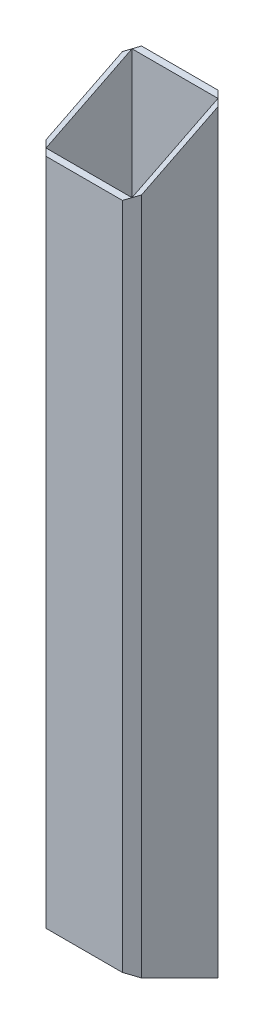
SolidWorks part; units mm, degrees
ref_plane "Front Plane" through (0, 0, 0) normal (0, 0, 1) x (1, 0, 0)
ref_plane "Top Plane" through (0, 0, 0) normal (0, 1, 0) x (1, 0, 0)
ref_plane "Right Plane" through (0, 0, 0) normal (1, 0, 0) x (0, 0, -1)
sketch "Sketch1" plane through (0, 0, 0) normal (0, 0, 1) x (1, 0, 0)
  line L1 (0, 0) -> (50, 0)
  line L2 (0, 0) -> (0, 400)
  line L3 (0, 400) -> (50, 400)
  line L4 (50, 0) -> (50, 400)
  dimension "D1" = 400
  dimension "D2" = 50
extrude "Boss-Extrude2" add sketch "Sketch1" along normal blind 50
sketch "Sketch2" plane through (0, 0, 0) normal (0, -1, 0) x (1, 0, 0)
  line L3 (2.5, 47.5) -> (47.5, 47.5)
  line L4 (47.5, 47.5) -> (47.5, 2.5)
  line L5 (47.5, 2.5) -> (2.5, 2.5)
  line L6 (2.5, 47.5) -> (2.5, 2.5)
extrude "Cut-Extrude1" cut sketch "Sketch2" against normal through all
sketch "Sketch3" plane through (0, 0, 0) normal (-1, 0, 0) x (0, 0, 1)
  line L0 (0, 400) -> (50, 400)
  line L1 (50, 400) -> (50, 375)
  line L2 (50, 400) -> (50, 0) construction
  line L3 (50, 375) -> (0, 400)
  line L4 (0, 0) -> (50, 0)
  line L5 (50, 0) -> (50, 25)
  line L6 (50, 25) -> (0, 0)
extrude "Cut-Extrude2" cut sketch "Sketch3" against normal through all contours L3 L0 L1 | L6 L4 L5
chamfer "Chamfer1" distance 5 angle 45 4 edges at (0, 200, 0) (0, 200, 50) (50, 200, 0) (50, 200, 50)
